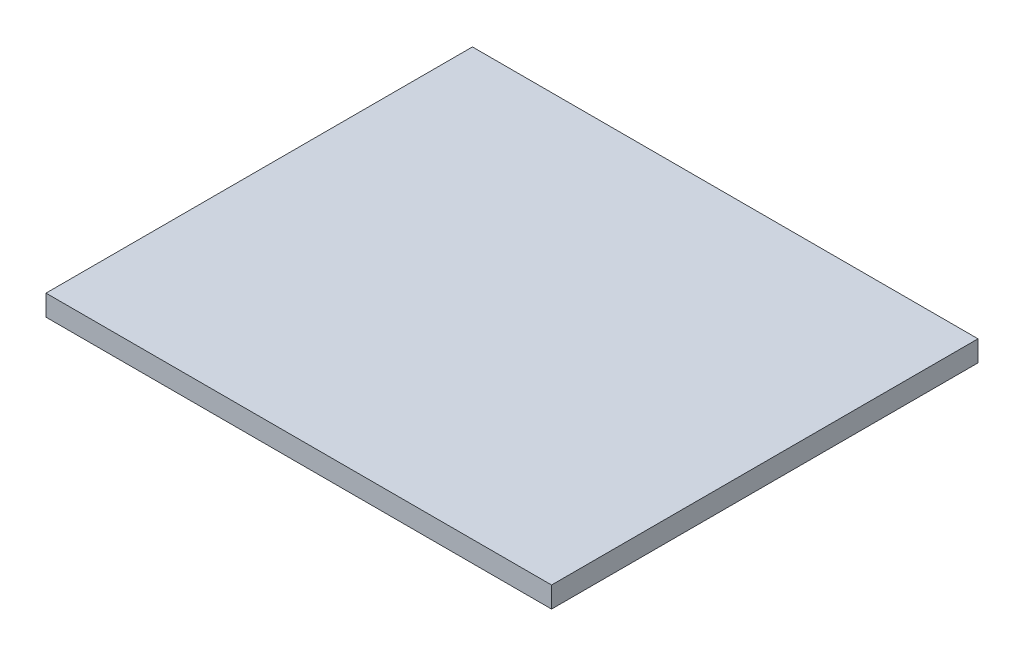
SolidWorks part; units mm, degrees
ref_plane "前视基准面" through (0, 0, 0) normal (0, 0, 1) x (1, 0, 0)
ref_plane "上视基准面" through (0, 0, 0) normal (0, 1, 0) x (1, 0, 0)
ref_plane "右视基准面" through (0, 0, 0) normal (1, 0, 0) x (0, 0, -1)
sketch "草图1" plane through (0, 0, 0) normal (0, 1, 0) x (1, 0, 0)
  line L1 (0, 0) -> (230, 0)
  line L2 (0, 0) -> (0, -194)
  line L3 (0, -194) -> (230, -194)
  line L4 (230, 0) -> (230, -194)
  dimension "D1" = 194
  dimension "D2" = 230
extrude "凸台-拉伸1" add sketch "草图1" along normal blind 9.5
sketch "草图2" plane through (0, 9.5, 0) normal (0, 1, 0) x (1, 0, 0)
  line L0 (0, -97) -> (230, -97) construction
  line L1 (0, 0) -> (0, -194) construction
  line L2 (230, -194) -> (230, 0) construction
ref_plane "基准面1" through (0, 0, 97) normal (0, 0, 1) x (1, 0, 0)
